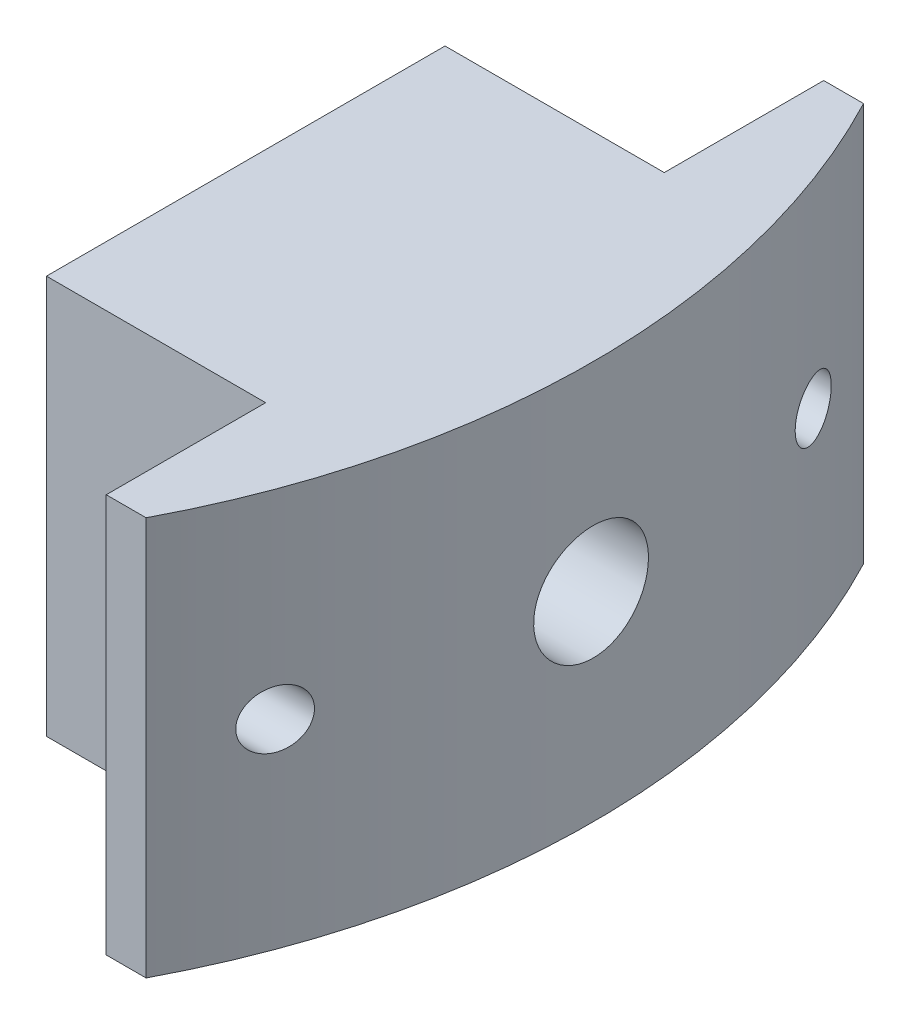
SolidWorks part; units mm, degrees
material "Plain Carbon Steel"
ref_plane "Front Plane" through (0, 0, 0) normal (0, 0, 1) x (1, 0, 0)
ref_plane "Top Plane" through (0, 0, 0) normal (0, 1, 0) x (1, 0, 0)
ref_plane "Right Plane" through (0, 0, 0) normal (1, 0, 0) x (0, 0, -1)
sketch "Sketch2" plane through (0, 0, 0) normal (0, 1, 0) x (1, 0, 0)
  line L0 (43.5809, 22.86) -> (43.5809, -22.86)
  line L1 (41.0409, 12.7) -> (41.0409, -12.7)
  line L2 (43.5809, 22.86) -> (41.0409, 22.86)
  line L3 (43.5809, 22.86) -> (43.5809, -22.86)
  line L4 (43.5809, -22.86) -> (41.0409, -22.86)
  line L5 (41.0409, 22.86) -> (41.0409, -22.86)
  line L6 (41.0409, 12.7) -> (27.0709, 12.7)
  line L11 (27.0709, 12.7) -> (27.0709, -12.7)
  line L12 (27.0709, -12.7) -> (41.0409, -12.7)
  line L13 (0, 0) -> (29.3279, 0) construction
  line L14 (0, 0) -> (47.5356, -12.7371) construction
  arc A0 (43.5809, -22.86) -> (43.5809, 22.86) centre (0, 0) ccw
  point P9 (41.0409, 0)
  dimension "D1" = 49.2125
  dimension "D2" = 45.72
  dimension "D3" = 2.54
  dimension "D4" = 25.4
  dimension "D5" = 13.97
  dimension "D6" = 15
extrude "Boss-Extrude1" add sketch "Sketch2" along normal blind 25.4 contours L11 L12 L1 L6 | L2 L5 L1 L4 L0 | L0 A0 | L0 A0 region at (45.8449, 0, 0) region at (42.3109, 0, 0) region at (34.0559, 0, 0)
ref_plane "Plane1" through (49.2125, 0, 0) normal (1, 0, 0) x (0, 0, -1)
sketch "Sketch4" plane through (27.0709, 0, 0) normal (-1, 0, 0) x (0, 0, 1)
  line L4 (-12.7, 0) -> (12.7, 25.4) construction
  line L5 (-12.7, 0) -> (12.7, 0) construction
  line L6 (-12.7, 25.4) -> (-12.7, 0) construction
  line L7 (-12.7, 25.4) -> (12.7, 0) construction
  line L8 (12.7, 25.4) -> (12.7, 0) construction
  line L9 (12.7, 25.4) -> (12.7, 0) construction
  circle A0 centre (0, 12.7) radius 3.81
  circle A1 centre (0, 12.7) radius 1.27
  point P15 (0, 12.7)
  dimension "D1" = 7.62
  dimension "D2" = 2.54
extrude "Cut-Extrude2" cut sketch "Sketch4" against normal up to next contours A1
sketch "Sketch11" plane through (41.0409, 0, 0) normal (-1, 0, 0) x (0, 0, 1)
  circle A2 centre (0, 12.7) radius 3.6576
  dimension "D3" = 7.3152
extrude "Cut-Extrude4" cut sketch "Sketch11" along normal blind 12.7 from surface contours A2 starting at plane "Plane1"
sketch "Sketch13" plane through (49.2125, 0, 0) normal (1, 0, 0) x (0, 0, -1)
  line L1 (-6.2992, 12.7) -> (-7.6327, 12.7) construction
  line L2 (-6.2992, 12.7) -> (-4.9657, 12.7) construction
  line L4 (0, 12.7) -> (-22.86, 12.7) construction
  line L5 (-22.86, 25.4) -> (-22.86, 0) construction
  circle A0 centre (0, 12.7) radius 4.9657
  circle A1 centre (0, 12.7) radius 7.6327
  circle A2 centre (0, 12.7) radius 6.2992 construction
  dimension "D1" = 12.5984
  dimension "D2" = 2.667
wrap "Wrap3" [suppressed] sketch "Sketch13" source sketch "Sketch13" thickness 1.3208 parameters "D1"=1.3208
sketch "Sketch15" plane through (0, 0, 0) normal (1, 0, 0) x (0, 0, -1)
  line L0 (-22.86, 12.7) -> (22.86, 12.7) construction
  line L1 (0, 0) -> (0, 25.4) construction
  line L4 (-22.86, 0) -> (22.86, 0)
  line L5 (22.86, 0) -> (22.86, 25.4)
  line L6 (22.86, 25.4) -> (-22.86, 25.4)
  line L7 (-22.86, 25.4) -> (-22.86, 0)
  line L8 (-22.86, 0) -> (22.86, 0)
  line L9 (22.86, 0) -> (22.86, 25.4)
  line L10 (22.86, 25.4) -> (-22.86, 25.4)
  line L11 (-22.86, 25.4) -> (-22.86, 0)
  circle A0 centre (-17.145, 12.7) radius 1.8288
  circle A1 centre (17.145, 12.7) radius 1.8288
  dimension "D2" = 3.6576
  dimension "D3" = 5.715
extrude "Cut-Extrude5" cut sketch "Sketch15" along normal up to surface (46.7684 mm away) contours L0 A0 | A1 region at (0, 12.7, 17.145) region at (0, 12.7, -17.145) up to face at (49.0834, 13.5299, 3.5622)
equation "\"Middle Coupler Inner Daimeter\"= 3.875in"
equation "\"Middle Coupler  Wall Thickness\" = 0.25in"
equation "\"Middle Coupler Bottom Thickness\"= 0.2in"
equation "\"Bearing Rail Offset\"= 0.45in"
equation "\"3-56 UNF Tap\"= 0.089in"
equation "\"3-48 Tap\"= 0.079in"
equation "\"3-56 UNF Clearance\"= 0.104in"
equation "\"3-48 Clearance\" = 0.104in"
equation "\"Ball Bearing Distance\"= 0.03in"
equation "\"TCA Outer Diameter\" = 6in"
equation "\"Interstage Aeroframe Wall Thickness\" = 0.072in"
equation "\"Compression Spring OD\"= 0.42in"
equation "\"10-24 Tap\"= 0.1495in"
equation "\"10-24 Clearance\"= 0.196in"
equation "\"Lower Stage Fuselage Wall Thickness\" = 0.25in"
equation "\"6-32 Tap\" = 0.107in"
equation "\"6-32 Clearance\" = 0.144in"
equation "\"1/4-20 Tap\" = 0.201in"
equation "\"12-24 Tap\" = 0.177in"
equation "\"D1@Sketch2\"=\"Middle Coupler Inner Daimeter\"/2"
equation "\"D2@Sketch15\"=\"6-32 Clearance\""
